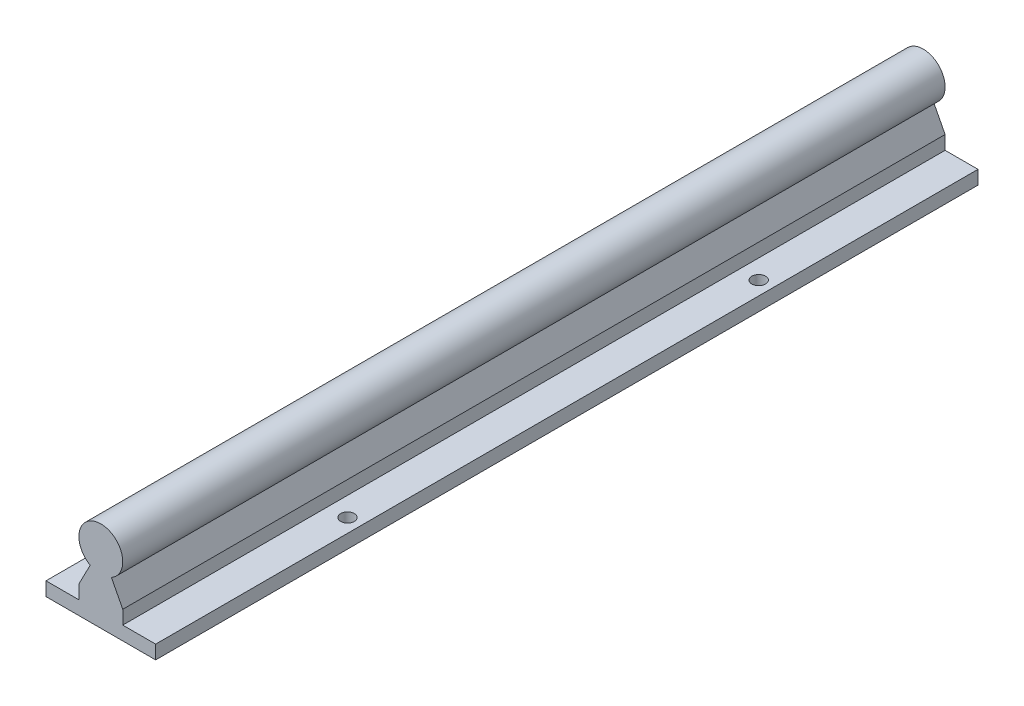
SolidWorks part; units mm, degrees
ref_plane "Front Plane" through (0, 0, 0) normal (0, 0, 1) x (1, 0, 0)
ref_plane "Top Plane" through (0, 0, 0) normal (0, 1, 0) x (1, 0, 0)
ref_plane "Right Plane" through (0, 0, 0) normal (1, 0, 0) x (0, 0, -1)
sketch "Sketch2" plane through (0, 0, 0) normal (0, 0, 1) x (1, 0, 0)
  line L0 (-20, 0) -> (20, 0)
  line L1 (20, 0) -> (20, 5)
  line L2 (-20, 0) -> (-20, 5)
  line L3 (-20, 5) -> (-8, 5)
  line L4 (20, 5) -> (8, 5)
  line L5 (-8, 5) -> (-8, 10)
  line L6 (8, 5) -> (8, 10)
  line L8 (-8, 10) -> (-3.873, 18)
  line L9 (8, 10) -> (3.873, 18)
  circle A0 centre (0, 25) radius 8
  dimension "D1" = 16
  dimension "D2" = 40
  dimension "D3" = 5
  dimension "D4" = 5
  dimension "D5" = 25
  dimension "D6" = 12
  dimension "D7" = 12
  dimension "D8" = 5
  dimension "D9" = 5
  dimension "D10" = 20
extrude "Boss-Extrude3" add sketch "Sketch2" along normal blind 300 contours A0 L8 L5 L3 L2 L0 L1 L4 L6 L9 region at (0, 6.2033, 0)
extrude "Boss-Extrude4" add sketch "Sketch2<4>" along normal blind 300 contours A0 region at (0, 25, 0)
sketch "Sketch2<4>" plane through (0, 0, 0) normal (0, 0, 1) x (1, 0, 0) same geometry as "Sketch2"
hole_wizard "Ø5.0mm Dowel Hole1" positions "Sketch4" profile "Sketch3" hole size "Ø5.0" standard "ISO" end condition through all
sketch "Sketch4" plane through (0, 5, 0) normal (0, 1, 0) x (1, 0, 0)
  line L0 (-20, -300) -> (-20, 0) construction
  line L1 (20, -300) -> (20, 0) construction
  line L2 (20, -300) -> (8, -300) construction
  line L3 (-20, -300) -> (-8, -300) construction
  point P0 (-15, -225)
  point P2 (15, -225)
  dimension "D1" = 5
  dimension "D2" = 5
  dimension "D3" = 75
  dimension "D4" = 75
sketch "Sketch3" plane through (-15, 5, 225) normal (1, 0, 0) x (0, 0, 1)
  line L0 (0, 0) -> (0, 5)
  line L1 (0, 5) -> (2.5, 5)
  line L2 (2.5, 5) -> (2.5, 0)
  line L5 (2.5, 0) -> (0, 0)
  line L11 (0, -6.35) -> (0, 107.95) construction
  dimension "Thru Hole Dia." = 5
  dimension "Thru Hole Depth" = 5
pattern_linear "LPattern1" count 2 spacing 150 along (0, 0, -1) of "Ø5.0mm Dowel Hole1"
